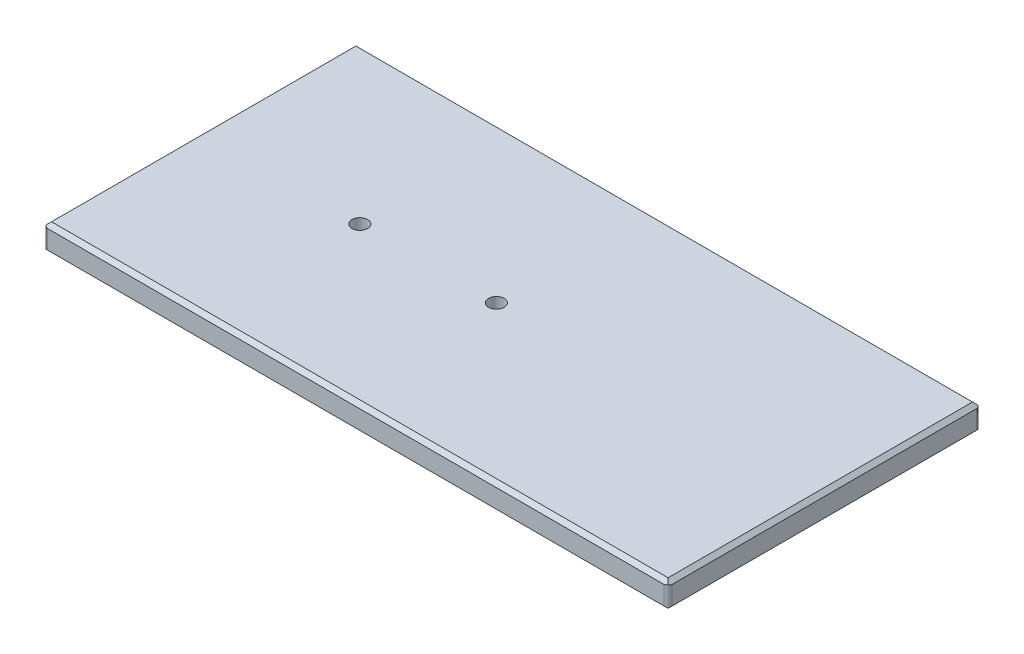
SolidWorks part; units mm, degrees
material "6061-T6 (SS)"
ref_plane "前视基准面" through (0, 0, 0) normal (0, 0, 1) x (1, 0, 0)
ref_plane "上视基准面" through (0, 0, 0) normal (0, 1, 0) x (1, 0, 0)
ref_plane "右视基准面" through (0, 0, 0) normal (1, 0, 0) x (0, 0, -1)
sketch "草图1" plane through (0, 0, 0) normal (0, 1, 0) x (1, 0, 0)
  line L1 (80, 40) -> (-80, 40)
  line L2 (80, 40) -> (80, -40)
  line L3 (80, -40) -> (-80, -40)
  line L4 (-80, 40) -> (-80, -40)
  line L5 (80, 40) -> (-80, -40) construction
  line L6 (80, -40) -> (-80, 40) construction
  point P0 (0, 0)
  dimension "D1" = 80
  dimension "D2" = 160
extrude "凸台-拉伸1" add sketch "草图1" along normal blind 6
chamfer "倒角1" distance 1 angle 45 4 edges at (0, 6, -40) (80, 6, 0) (0, 6, 40) (-80, 6, 0)
chamfer "倒角2" distance 0.2 angle 45 4 edges at (0, 0, 40) (80, 0, 0) (0, 0, -40) (-80, 0, 0)
sketch "草图2" plane through (0, 6, 0) normal (0, 1, 0) x (1, 0, 0)
  line L0 (80, -40) -> (-80, -40) construction
  line L1 (-80, -40) -> (-80, 40) construction
  circle A0 centre (-45, -27) radius 2
  circle A1 centre (11, -27) radius 2
  dimension "D1" = 4
  dimension "D2" = 56
  dimension "D3" = 13
  dimension "D4" = 35
sketch "草图3" plane through (0, 6, 0) normal (0, 1, 0) x (1, 0, 0)
  line L0 (80, -40) -> (-80, -40) construction
  line L1 (-80, -40) -> (-80, 40) construction
  circle A0 centre (-39, 0) radius 2
  circle A1 centre (-4, 0) radius 2
  dimension "D1" = 4
  dimension "D4" = 35
  dimension "D2" = 40
  dimension "D3" = 41
extrude "切除-拉伸2" cut sketch "草图3" against normal through all
chamfer "倒角4" distance 0.5 angle 45 2 edges at (-39, 0, 2) (-4, 0, 2)
sketch "草图4" plane through (0, 6, 0) normal (0, 1, 0) x (1, 0, 0)
  line L0 (-80, 40) -> (80, 40) construction
  line L1 (80, 40) -> (80, -40) construction
  circle A0 centre (59, 18) radius 1.5
  dimension "D1" = 3
  dimension "D2" = 22
  dimension "D3" = 21
fillet "圆角1" radius 1 4 edges at (-80, 2.6, -40) (80, 2.6, -40) (80, 2.6, 40) (-80, 2.6, 40)
sketch "草图5" plane through (0, 0, 0) normal (0, -1, 0) x (1, 0, 0)
  line L1 (-79.8, 39.6) -> (-79.8, -39.6) construction
  line L2 (68.8, -29) -> (-68.8, -29) construction
  line L3 (68.8, -29) -> (68.8, 29) construction
  line L4 (68.8, 29) -> (-68.8, 29) construction
  line L5 (-68.8, -29) -> (-68.8, 29) construction
  line L6 (68.8, -29) -> (-68.8, 29) construction
  line L7 (68.8, 29) -> (-68.8, -29) construction
  line L8 (79, -40) -> (-79, -40) construction
  circle A0 centre (-68.8, 29) radius 9.5 construction
  point P2 (0, 0)
  dimension "D3" = 19
  dimension "D1" = 11
  dimension "D2" = 11
equation "\"马达固定中心距\"= 56"
equation "\"支架固定中心距\"= 35"
equation "\"D2@草图2\"=\"马达固定中心距\""
equation "\"D4@草图3\"=\"支架固定中心距\""
